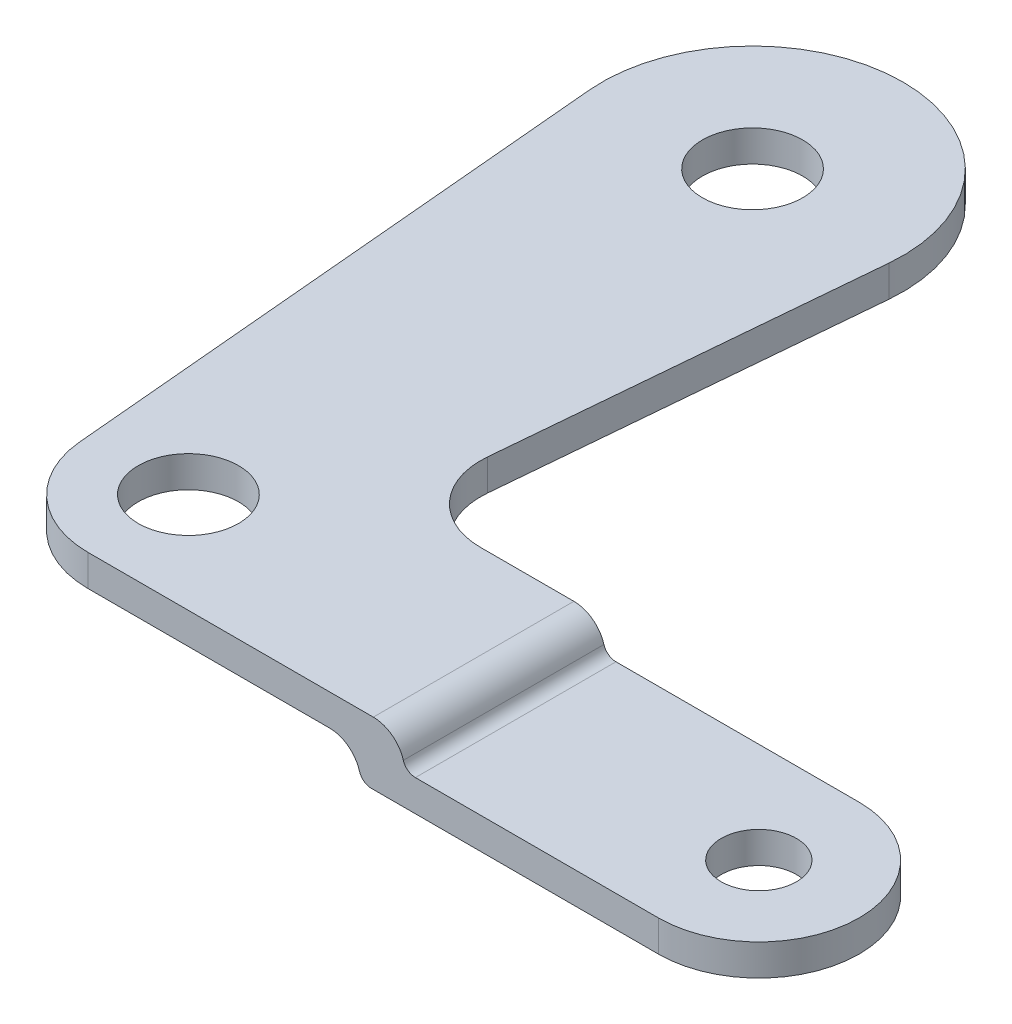
SolidWorks part; units mm, degrees
ref_plane "Front Plane" through (0, 0, 0) normal (0, 0, 1) x (1, 0, 0)
ref_plane "Top Plane" through (0, 0, 0) normal (0, 1, 0) x (1, 0, 0)
ref_plane "Right Plane" through (0, 0, 0) normal (1, 0, 0) x (0, 0, -1)
sketch "Sketch1" plane through (0, 0, 0) normal (0, 1, 0) x (1, 0, 0)
  line L0 (45.5, 0) -> (0, 0) construction
  line L1 (0, 0) -> (0, 45) construction
  line L2 (45.5, 8) -> (45.5, -8) construction
  line L3 (45.5, -8) -> (0, -8)
  line L4 (-11.9525, 43.9333) -> (-7.9683, -0.7111)
  line L5 (11.9525, 43.9333) -> (9.3288, 14.5333)
  line L6 (45.5, 8) -> (15.305, 8)
  line L7 (22.75, 8) -> (22.75, -8)
  circle A0 centre (45.5, 0) radius 3
  circle A1 centre (0, 0) radius 4
  circle A2 centre (0, 45) radius 4
  arc A3 (45.5, 8) -> (45.5, -8) centre (45.5, 0) cw
  arc A4 (11.9524, 43.9325) -> (-11.9525, 43.9333) centre (0, 45) ccw
  arc A5 (0, -8) -> (-7.9683, -0.7111) centre (0, 0) cw
  arc A6 (15.305, 8) -> (9.3288, 14.5333) centre (15.305, 14) cw
  dimension "D3" = 6
  dimension "D4" = 8
  dimension "D5" = 8
  dimension "D6" = 8
  dimension "D7" = 12
  dimension "D8" = 6
  dimension "D1" = 45.5
  dimension "D2" = 45
extrude "Boss-Extrude1" add sketch "Sketch1" along normal blind 2.5 contours A3 L6 L7 L3 A0 region at (36.7914, 0, 0)
extrude "Boss-Extrude2" add sketch "Sketch1<3>" along normal blind 2.5 from surface separate body contours L6 A6 L5 A4 L4 A5 L3 L7 A2 A1 region at (2.7322, 0, -21.9361) starting at face at (36.125, 2.5, 0)
sketch "Sketch1<3>" plane through (0, 0, 0) normal (0, 1, 0) x (1, 0, 0) same geometry as "Sketch1"
sketch "Sketch2" plane through (0, 0, 8) normal (0, 0, 1) x (1, 0, 0)
  line L0 (19.25, 5) -> (19.25, 2.5)
  line L1 (26.25, 2.5) -> (26.25, 0)
  line L2 (26.25, 0) -> (22.6041, 0)
  line L3 (26.25, 2.5) -> (26.1041, 2.5)
  line L4 (22.75, 5) -> (19.25, 5)
  line L5 (45.5, 0) -> (22.75, 0) construction
  line L7 (45.5, 2.5) -> (22.75, 2.5) construction
  line L8 (0, 5) -> (22.75, 5) construction
  line L9 (0, 2.5) -> (22.75, 2.5) construction
  arc A0 (22.75, 5) -> (25.1458, 3.2143) centre (22.75, 2.5) cw
  arc A1 (19.25, 2.5) -> (21.6458, 0.7143) centre (19.25, 0) cw
  arc A2 (21.6458, 0.7143) -> (22.6041, 0) centre (22.6041, 1) ccw
  arc A3 (25.1458, 3.2143) -> (26.1041, 2.5) centre (26.1041, 3.5) ccw
  line M12 (45.5, 2.5) -> (22.75, 2.5)
  line M13 (22.75, 2.5) -> (22.75, 0)
  dimension "D1" = 1
  dimension "D3" = 2.5
  dimension "D4" = 2.5
  dimension "D2" = 3.5
extrude "Boss-Extrude3" add sketch "Sketch2" along direction (0, 0, 1) on the side against the normal blind 16 contours A3 A0 L4 L0 A1 A2 L2 M13 M12 region at (22.008, 3.22, 8)
